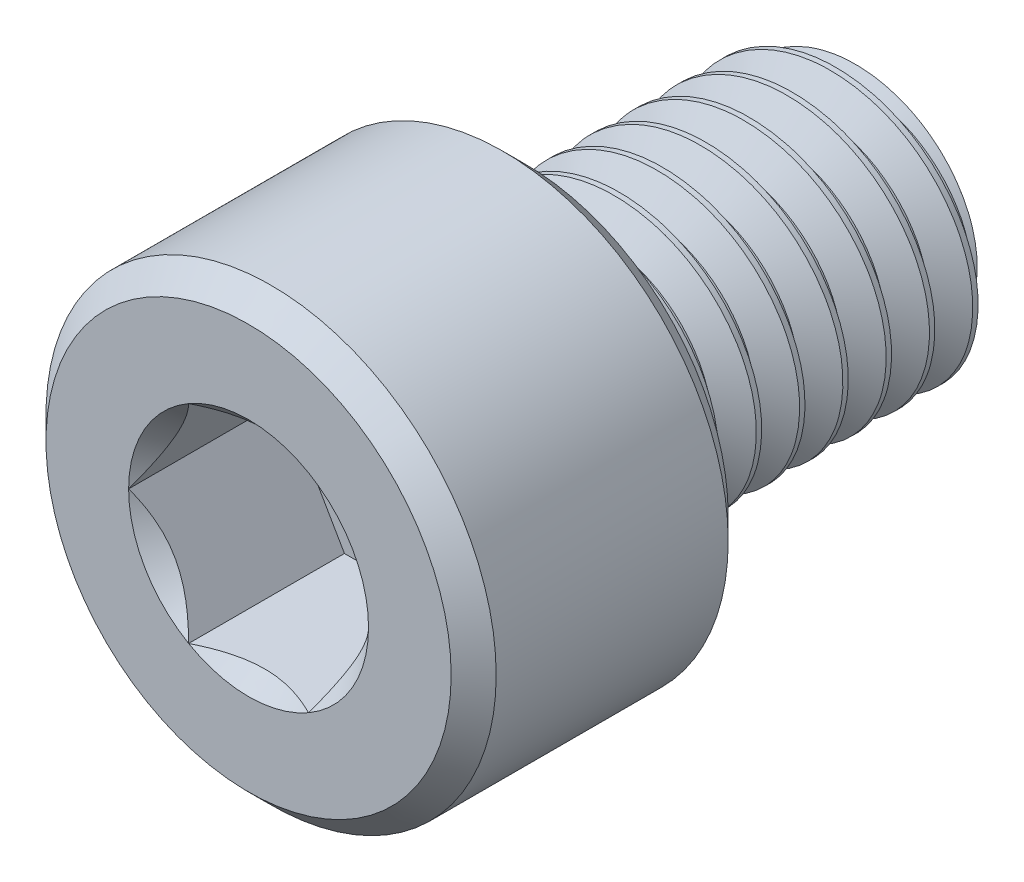
SolidWorks part; units mm, degrees
ref_plane "Front Plane" through (0, 0, 0) normal (0, 0, 1) x (1, 0, 0)
ref_plane "Top Plane" through (0, 0, 0) normal (0, 1, 0) x (1, 0, 0)
ref_plane "Right Plane" through (0, 0, 0) normal (1, 0, 0) x (0, 0, -1)
sketch "Sketch1" plane through (0, 0, 0) normal (0, 0, 1) x (1, 0, 0)
  circle A0 centre (0, 0) radius 4
  dimension "BODY DIAMETER" = 8
extrude "Boss-Extrude1" add sketch "Sketch1" along normal blind 10
sketch "Sketch2" plane through (0, 0, 0) normal (0, 0, -1) x (-1, 0, 0)
  circle A1 centre (0, 0) radius 4
  circle A2 centre (0, 0) radius 4
  dimension "D1" = 0
curve "Helix/Spiral1" pitch 1.25 height 45 turns 36 parameters "PITCH"=1.25
ref_plane "Plane1" through (0, 4, 0) normal (-0.9988, 0, 0.0497) x (0.0497, 0, 0.9988)
sketch "Sketch3" plane through (0, 4, 0) normal (-0.9988, 0, 0.0497) x (0.0497, 0, 0.9988)
  line L0 (0, 0) -> (-1.094, 0)
  line L1 (-1.094, 0) -> (-0.625, -0.8123)
  line L2 (-0.625, -0.8123) -> (-0.469, -0.8123)
  line L3 (-0.469, -0.8123) -> (0, 0)
  line L4 (-0.547, -0.8123) -> (-0.547, 0) construction
  line L5 (-0.8595, -0.4062) -> (-0.2345, -0.4062) construction
  dimension "D1" = 60
  dimension "THREAD DIM1" = 0.156
  dimension "THREAD DIM 2" = 0.625
sweep "Cut-Sweep1" cut profiles "Sketch3" path "Helix/Spiral1" align with end faces yes
sketch "Sketch4" plane through (0, 0, 0) normal (1, 0, 0) x (0, 0, -1)
  line L0 (0, 5) -> (-1.4469, 5)
  line L1 (-1.4469, 5) -> (0, 2.9337)
  line L2 (0, 2.9337) -> (0, 5)
  line L3 (0, 4) -> (1.0926, 4) construction
  line L4 (0, 0) -> (1.7976, 0) construction
  dimension "D1" = 55
  dimension "D2" = 1
  dimension "D3" = 0.254
revolve "Cut-Revolve1" cut sketch "Sketch4" angle 360 about L4
sketch "Sketch5" plane through (0, 0, 10) normal (0, 0, 1) x (1, 0, 0)
  circle A0 centre (0, 0) radius 6.5
  dimension "HEAD DIAMETER" = 13
extrude "Boss-Extrude2" add sketch "Sketch5" along normal blind 8
sketch "Sketch6" plane through (0, 0, 18) normal (0, 0, 1) x (1, 0, 0)
  line L1 (1.7321, 3) -> (-1.7321, 3)
  line L2 (-1.7321, 3) -> (-3.4641, 0)
  line L3 (-3.4641, 0) -> (-1.7321, -3)
  line L4 (-1.7321, -3) -> (1.7321, -3)
  line L5 (1.7321, -3) -> (3.4641, 0)
  line L6 (3.4641, 0) -> (1.7321, 3)
  circle A0 centre (0, 0) radius 3 construction
  dimension "HEX SOCKET SIZE" = 6
extrude "Cut-Extrude1" cut sketch "Sketch6" against normal blind 4.5
sketch "Sketch7" plane through (0, 0, 18) normal (0, 0, 1) x (1, 0, 0)
  circle A0 centre (0, 0) radius 3.4641
extrude "Cut-Extrude2" cut sketch "Sketch7" against normal through all draft 45
chamfer "Chamfer1" distance 0.65 angle 45 2 edges at (6.5, 0, 10) (6.5, 0, 18)
